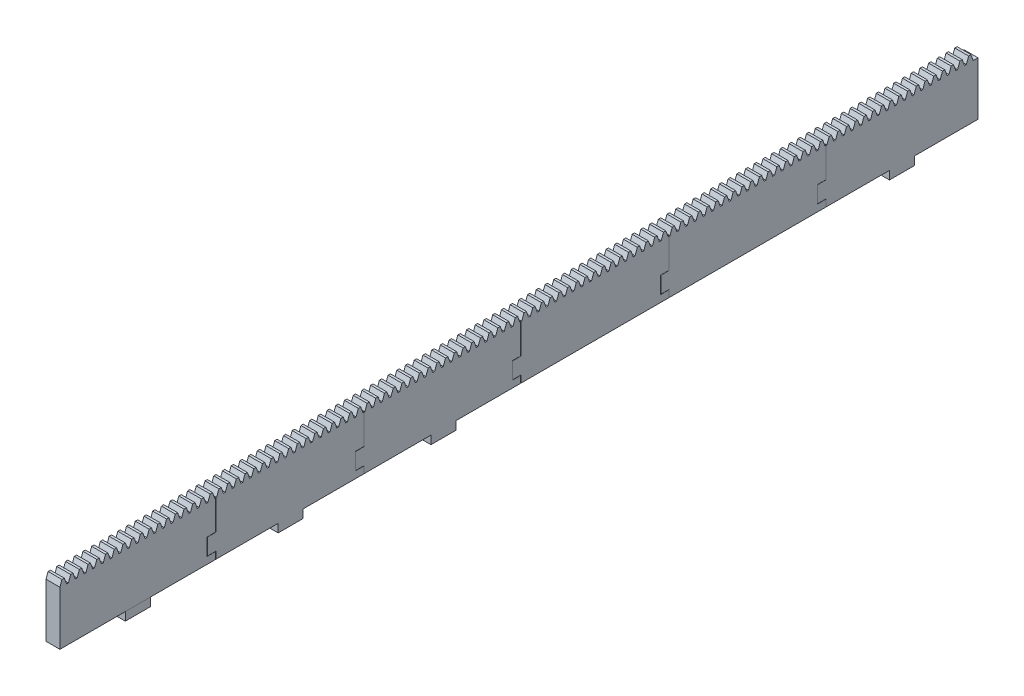
SolidWorks part; units mm, degrees
ref_plane "Спереди" through (0, 0, 0) normal (0, 0, 1) x (1, 0, 0)
ref_plane "Сверху" through (0, 0, 0) normal (0, 1, 0) x (1, 0, 0)
ref_plane "Справа" through (0, 0, 0) normal (1, 0, 0) x (0, 0, -1)
sketch "Эскиз2" plane through (0, 0, 0) normal (1, 0, 0) x (0, 0, -1)
  line L0 (-26.55, -90810.0672) -> (-26.55, -90381.6872) construction
  line L1 (-26.55, -90933.2872) -> (635.45, -90933.2872)
  line L2 (-26.55, -90933.2872) -> (-26.55, -90894.9119)
  line L3 (-26.55, -90894.9119) -> (635.45, -90894.9119)
  line L4 (635.45, -90933.2872) -> (635.45, -90894.9119)
  line L5 (635.45, -90810.0672) -> (635.45, -90381.6872) construction
  line L7 (-26.55, -90933.2872) -> (635.45, -90933.2872) construction
  dimension "D1" = 38.3753
  dimension "База_начала" = 26.55
  dimension "Длина_базы" = 662
  dimension "База_конца" = 635.45
  dimension "База_низа" = 90933.2872
extrude "Бобышка-Вытянуть1" add sketch "Эскиз2" along normal blind 10
sketch "Эскиз3" plane through (10, 0, 0) normal (1, 0, 0) x (0, 0, -1)
  line L0 (-26.55, -90894.9119) -> (-24.9125, -90890.4119)
  line L2 (-24.9125, -90890.4119) -> (-23.2265, -90890.4119)
  line L3 (-23.2265, -90890.4119) -> (-21.589, -90894.9119)
  line L4 (635.45, -90894.9119) -> (-26.55, -90894.9119) construction
  line L5 (-21.589, -90894.9119) -> (-26.55, -90894.9119)
  line L6 (-24.0695, -90890.4119) -> (-24.0695, -90894.9119) construction
  line L7 (-26.55, -90894.9119) -> (-26.55, -90933.2872) construction
  dimension "D1" = 1.686
  dimension "D2" = 4.961
  dimension "D3" = 4.5
extrude "Бобышка-Вытянуть2" add sketch "Эскиз3" against normal blind 10
pattern_linear "Линейный массив1" count 105 spacing 6.2832 along (0, 0, -1) of "Бобышка-Вытянуть2"
sketch "Лапки_рейки_эскиз" plane through (0, 0, 0) normal (1, 0, 0) x (0, 0, -1)
  line L0 (590.5046, -90933.2872) -> (570.5046, -90933.2872)
  line L1 (570.5046, -90933.2872) -> (570.5046, -90925.2872)
  line L2 (570.5046, -90925.2872) -> (590.5046, -90925.2872)
  line L3 (590.5046, -90925.2872) -> (590.5046, -90933.2872)
  line L4 (479.1606, -90933.2872) -> (459.1606, -90933.2872)
  line L5 (459.1606, -90933.2872) -> (459.1606, -90925.2872)
  line L6 (459.1606, -90925.2872) -> (479.1606, -90925.2872)
  line L7 (479.1606, -90925.2872) -> (479.1606, -90933.2872)
  line L8 (369.2048, -90933.2872) -> (349.2048, -90933.2872)
  line L9 (349.2048, -90933.2872) -> (349.2048, -90925.2872)
  line L10 (349.2048, -90925.2872) -> (369.2048, -90925.2872)
  line L11 (369.2048, -90925.2872) -> (369.2048, -90933.2872)
  line L12 (259.2491, -90933.2872) -> (239.2491, -90933.2872)
  line L13 (239.2491, -90933.2872) -> (239.2491, -90925.2872)
  line L14 (239.2491, -90925.2872) -> (259.2491, -90925.2872)
  line L15 (259.2491, -90925.2872) -> (259.2491, -90933.2872)
  line L16 (149.2933, -90933.2872) -> (129.2933, -90933.2872)
  line L17 (129.2933, -90933.2872) -> (129.2933, -90925.2872)
  line L18 (129.2933, -90925.2872) -> (149.2933, -90925.2872)
  line L19 (149.2933, -90925.2872) -> (149.2933, -90933.2872)
  line L20 (39.7431, -90933.2872) -> (19.7431, -90933.2872)
  line L21 (19.7431, -90933.2872) -> (19.7431, -90925.2872)
  line L22 (19.7431, -90925.2872) -> (39.7431, -90925.2872)
  line L23 (39.7431, -90925.2872) -> (39.7431, -90933.2872)
  dimension "X001" = 19.7431
  dimension "X002" = 20
  dimension "X003" = 89.5502
  dimension "X004" = 20
  dimension "X005" = 89.9557
  dimension "X006" = 20
  dimension "X007" = 89.9557
  dimension "X008" = 20
  dimension "X009" = 89.9557
  dimension "X010" = 20
  dimension "X011" = 91.3441
  dimension "X012" = 20
  dimension "Y001" = 90933.2872
  dimension "Y002" = 8
extrude "Лапки_рейки_к_полу" add sketch "Лапки_рейки_эскиз" against normal blind 22
sketch "Шипы_рейки_эскиз" plane through (0, 0, 0) normal (1, 0, 0) x (0, 0, -1)
  line L0 (548.0184, -90937.2872) -> (530.0184, -90937.2872)
  line L1 (530.0184, -90937.2872) -> (530.0184, -90933.2772)
  line L2 (530.0184, -90933.2772) -> (548.0184, -90933.2772)
  line L3 (548.0184, -90933.2772) -> (548.0184, -90937.2872)
  line L4 (436.6743, -90937.2872) -> (418.6743, -90937.2872)
  line L5 (418.6743, -90937.2872) -> (418.6743, -90933.2772)
  line L6 (418.6743, -90933.2772) -> (436.6743, -90933.2772)
  line L7 (436.6743, -90933.2772) -> (436.6743, -90937.2872)
  line L8 (326.7186, -90937.2872) -> (308.7186, -90937.2872)
  line L9 (308.7186, -90937.2872) -> (308.7186, -90933.2772)
  line L10 (308.7186, -90933.2772) -> (326.7186, -90933.2772)
  line L11 (326.7186, -90933.2772) -> (326.7186, -90937.2872)
  line L12 (216.7628, -90937.2872) -> (198.7628, -90937.2872)
  line L13 (198.7628, -90937.2872) -> (198.7628, -90933.2772)
  line L14 (198.7628, -90933.2772) -> (216.7628, -90933.2772)
  line L15 (216.7628, -90933.2772) -> (216.7628, -90937.2872)
  line L16 (106.8071, -90937.2872) -> (88.8071, -90937.2872)
  line L17 (88.8071, -90937.2872) -> (88.8071, -90933.2772)
  line L18 (88.8071, -90933.2772) -> (106.8071, -90933.2772)
  line L19 (106.8071, -90933.2772) -> (106.8071, -90937.2872)
  line L20 (-2.7431, -90937.2872) -> (-20.7431, -90937.2872)
  line L21 (-20.7431, -90937.2872) -> (-20.7431, -90933.2772)
  line L22 (-20.7431, -90933.2772) -> (-2.7431, -90933.2772)
  line L23 (-2.7431, -90933.2772) -> (-2.7431, -90937.2872)
  dimension "X001" = 20.7431
  dimension "X002" = 18
  dimension "X003" = 91.5502
  dimension "X004" = 18
  dimension "X005" = 91.9557
  dimension "X006" = 18
  dimension "X007" = 91.9557
  dimension "X008" = 18
  dimension "X009" = 91.9557
  dimension "X010" = 18
  dimension "X011" = 93.3441
  dimension "X012" = 18
  dimension "Y001" = 90937.2872
  dimension "Y002" = 4.01
extrude "Шипы_рейки_4мм" [suppressed] add sketch "Шипы_рейки_эскиз" along normal blind 10
sketch "Болты_рейки_эскиз" plane through (0, 0, 0) normal (0, 1, 0) x (1, 0, 0)
  line L0 (-22, 39.7431) -> (0, 19.7431) construction
  line L1 (-22, 19.7431) -> (0, 19.7431) construction
  line L2 (0, 0.2202) -> (-22, 19.7431) construction
  line L3 (0, 39.7431) -> (0, 19.7431) construction
  circle A0 centre (-11, 580.5046) radius 2.75
  circle A1 centre (-11, 469.1606) radius 2.75
  circle A2 centre (-11, 359.2048) radius 2.75
  circle A3 centre (-11, 249.2491) radius 2.75
  circle A4 centre (-11, 139.2933) radius 2.75
  circle A5 centre (-11, 29.7431) radius 2.75
  point P26 (-11, 29.7431)
  dimension "Диаметр001" = 5.5
  dimension "Диаметр002" = 5.5
  dimension "Диаметр003" = 5.5
  dimension "Диаметр004" = 5.5
  dimension "Диаметр005" = 5.5
  dimension "Диаметр006" = 5.5
  dimension "Y002" = 109.5502
  dimension "Y003" = 109.9557
  dimension "Y004" = 109.9557
  dimension "Y005" = 109.9557
  dimension "Y006" = 111.3441
extrude "Болты_рейки_М5" cut sketch "Болты_рейки_эскиз" against normal through all and the other way through all
sketch "Гайки_рейки_эскиз" plane through (0, -90925.2872, 0) normal (0, 1, 0) x (1, 0, 0)
  line L0 (-6.208, 580.5046) -> (-8.604, 576.3546)
  line L1 (-8.604, 576.3546) -> (-13.396, 576.3546)
  line L2 (-13.396, 576.3546) -> (-15.792, 580.5046)
  line L3 (-15.792, 580.5046) -> (-13.396, 584.6546)
  line L4 (-13.396, 584.6546) -> (-8.604, 584.6546)
  line L5 (-8.604, 584.6546) -> (-6.208, 580.5046)
  line L6 (-6.208, 469.1606) -> (-8.604, 465.0106)
  line L7 (-8.604, 465.0106) -> (-13.396, 465.0106)
  line L8 (-13.396, 465.0106) -> (-15.792, 469.1606)
  line L9 (-15.792, 469.1606) -> (-13.396, 473.3106)
  line L10 (-13.396, 473.3106) -> (-8.604, 473.3106)
  line L11 (-8.604, 473.3106) -> (-6.208, 469.1606)
  line L12 (-6.208, 359.2048) -> (-8.604, 355.0548)
  line L13 (-8.604, 355.0548) -> (-13.396, 355.0548)
  line L14 (-13.396, 355.0548) -> (-15.792, 359.2048)
  line L15 (-15.792, 359.2048) -> (-13.396, 363.3548)
  line L16 (-13.396, 363.3548) -> (-8.604, 363.3548)
  line L17 (-8.604, 363.3548) -> (-6.208, 359.2048)
  line L18 (-6.208, 249.2491) -> (-8.604, 245.0991)
  line L19 (-8.604, 245.0991) -> (-13.396, 245.0991)
  line L20 (-13.396, 245.0991) -> (-15.792, 249.2491)
  line L21 (-15.792, 249.2491) -> (-13.396, 253.3991)
  line L22 (-13.396, 253.3991) -> (-8.604, 253.3991)
  line L23 (-8.604, 253.3991) -> (-6.208, 249.2491)
  line L24 (-6.208, 139.2933) -> (-8.604, 135.1433)
  line L25 (-8.604, 135.1433) -> (-13.396, 135.1433)
  line L26 (-13.396, 135.1433) -> (-15.792, 139.2933)
  line L27 (-15.792, 139.2933) -> (-13.396, 143.4433)
  line L28 (-13.396, 143.4433) -> (-8.604, 143.4433)
  line L29 (-8.604, 143.4433) -> (-6.208, 139.2933)
  line L30 (-6.208, 29.7431) -> (-8.604, 25.5931)
  line L31 (-8.604, 25.5931) -> (-13.396, 25.5931)
  line L32 (-13.396, 25.5931) -> (-15.792, 29.7431)
  line L33 (-15.792, 29.7431) -> (-13.396, 33.8931)
  line L34 (-13.396, 33.8931) -> (-8.604, 33.8931)
  line L35 (-8.604, 33.8931) -> (-6.208, 29.7431)
  line L36 (-22, 39.7431) -> (-22, 19.7431) construction
  point P41 (-22, 29.7431)
  dimension "X001" = 15.792
  dimension "X002" = 2.396
  dimension "X003" = 4.792
  dimension "X004" = 2.396
  dimension "Y002" = 4.15
  dimension "Y003" = 4.15
  dimension "Y004" = 101.2502
  dimension "Y005" = 4.15
  dimension "Y006" = 4.15
  dimension "Y007" = 101.6557
  dimension "Y008" = 4.15
  dimension "Y009" = 4.15
  dimension "Y010" = 101.6557
  dimension "Y011" = 4.15
  dimension "Y012" = 4.15
  dimension "Y013" = 101.6557
  dimension "Y014" = 4.15
  dimension "Y015" = 4.15
  dimension "Y016" = 103.0441
  dimension "Y017" = 4.15
  dimension "Y018" = 4.15
extrude "Гайки_рейки_М5_4_3мм" cut sketch "Гайки_рейки_эскиз" against normal blind 4.3
sketch "Секции_рейки_эскиз" plane through (0, 0, 0) normal (1, 0, 0) x (0, 0, -1)
  line L0 (525.7842, -90938.2872) -> (525.6342, -90938.2872)
  line L1 (525.6342, -90938.2872) -> (525.6342, -90928.3622)
  line L2 (525.6342, -90928.3622) -> (519.6342, -90928.3622)
  line L3 (519.6342, -90928.3622) -> (519.6342, -90916.2122)
  line L4 (519.6342, -90916.2122) -> (525.6342, -90916.2122)
  line L5 (525.6342, -90916.2122) -> (525.6342, -90888.2872)
  line L6 (525.6342, -90888.2872) -> (525.7842, -90888.2872)
  line L7 (525.7842, -90888.2872) -> (525.7842, -90916.3622)
  line L8 (525.7842, -90916.3622) -> (519.7842, -90916.3622)
  line L9 (519.7842, -90916.3622) -> (519.7842, -90928.2122)
  line L10 (519.7842, -90928.2122) -> (525.7842, -90928.2122)
  line L11 (525.7842, -90928.2122) -> (525.7842, -90938.2872)
  line L12 (412.6869, -90938.2872) -> (412.5369, -90938.2872)
  line L13 (412.5369, -90938.2872) -> (412.5369, -90928.3622)
  line L14 (412.5369, -90928.3622) -> (406.5369, -90928.3622)
  line L15 (406.5369, -90928.3622) -> (406.5369, -90916.2122)
  line L16 (406.5369, -90916.2122) -> (412.5369, -90916.2122)
  line L17 (412.5369, -90916.2122) -> (412.5369, -90888.2872)
  line L18 (412.5369, -90888.2872) -> (412.6869, -90888.2872)
  line L19 (412.6869, -90888.2872) -> (412.6869, -90916.3622)
  line L20 (412.6869, -90916.3622) -> (406.6869, -90916.3622)
  line L21 (406.6869, -90916.3622) -> (406.6869, -90928.2122)
  line L22 (406.6869, -90928.2122) -> (412.6869, -90928.2122)
  line L23 (412.6869, -90928.2122) -> (412.6869, -90938.2872)
  line L24 (305.8727, -90938.2872) -> (305.7227, -90938.2872)
  line L25 (305.7227, -90938.2872) -> (305.7227, -90928.3622)
  line L26 (305.7227, -90928.3622) -> (299.7227, -90928.3622)
  line L27 (299.7227, -90928.3622) -> (299.7227, -90916.2122)
  line L28 (299.7227, -90916.2122) -> (305.7227, -90916.2122)
  line L29 (305.7227, -90916.2122) -> (305.7227, -90888.2872)
  line L30 (305.7227, -90888.2872) -> (305.8727, -90888.2872)
  line L31 (305.8727, -90888.2872) -> (305.8727, -90916.3622)
  line L32 (305.8727, -90916.3622) -> (299.8727, -90916.3622)
  line L33 (299.8727, -90916.3622) -> (299.8727, -90928.2122)
  line L34 (299.8727, -90928.2122) -> (305.8727, -90928.2122)
  line L35 (305.8727, -90928.2122) -> (305.8727, -90938.2872)
  line L36 (192.7754, -90938.2872) -> (192.6254, -90938.2872)
  line L37 (192.6254, -90938.2872) -> (192.6254, -90928.3622)
  line L38 (192.6254, -90928.3622) -> (186.6254, -90928.3622)
  line L39 (186.6254, -90928.3622) -> (186.6254, -90916.2122)
  line L40 (186.6254, -90916.2122) -> (192.6254, -90916.2122)
  line L41 (192.6254, -90916.2122) -> (192.6254, -90888.2872)
  line L42 (192.6254, -90888.2872) -> (192.7754, -90888.2872)
  line L43 (192.7754, -90888.2872) -> (192.7754, -90916.3622)
  line L44 (192.7754, -90916.3622) -> (186.7754, -90916.3622)
  line L45 (186.7754, -90916.3622) -> (186.7754, -90928.2122)
  line L46 (186.7754, -90928.2122) -> (192.7754, -90928.2122)
  line L47 (192.7754, -90928.2122) -> (192.7754, -90938.2872)
  line L48 (85.9612, -90938.2872) -> (85.8112, -90938.2872)
  line L49 (85.8112, -90938.2872) -> (85.8112, -90928.3622)
  line L50 (85.8112, -90928.3622) -> (79.8112, -90928.3622)
  line L51 (79.8112, -90928.3622) -> (79.8112, -90916.2122)
  line L52 (79.8112, -90916.2122) -> (85.8112, -90916.2122)
  line L53 (85.8112, -90916.2122) -> (85.8112, -90888.2872)
  line L54 (85.8112, -90888.2872) -> (85.9612, -90888.2872)
  line L55 (85.9612, -90888.2872) -> (85.9612, -90916.3622)
  line L56 (85.9612, -90916.3622) -> (79.9612, -90916.3622)
  line L57 (79.9612, -90916.3622) -> (79.9612, -90928.2122)
  line L58 (79.9612, -90928.2122) -> (85.9612, -90928.2122)
  line L59 (85.9612, -90928.2122) -> (85.9612, -90938.2872)
  dimension "X001" = 79.8112
  dimension "X002" = 0.15
  dimension "X003" = 5.85
  dimension "X004" = 0.15
  dimension "X005" = 100.6642
  dimension "X006" = 0.15
  dimension "X007" = 5.85
  dimension "X008" = 0.15
  dimension "X009" = 106.9473
  dimension "X010" = 0.15
  dimension "X011" = 5.85
  dimension "X012" = 0.15
  dimension "X013" = 100.6642
  dimension "X014" = 0.15
  dimension "X015" = 5.85
  dimension "X016" = 0.15
  dimension "X017" = 106.9473
  dimension "X018" = 0.15
  dimension "X019" = 5.85
  dimension "X020" = 0.15
  dimension "Y001" = 90938.2872
  dimension "Y002" = 9.925
  dimension "Y003" = 0.15
  dimension "Y004" = 11.85
  dimension "Y005" = 0.15
  dimension "Y006" = 27.925
extrude "Секции_рейки_шип_паз_6шт" cut sketch "Секции_рейки_эскиз" against normal through all and the other way through all
sketch "Торцы_рейки_эскиз" plane through (0, 0, 0) normal (1, 0, 0) x (0, 0, -1)
  line L0 (647.2604, -90939.2872) -> (635.3, -90939.2872)
  line L1 (635.3, -90939.2872) -> (635.3, -90883.2872)
  line L2 (635.3, -90883.2872) -> (647.2604, -90883.2872)
  line L3 (647.2604, -90883.2872) -> (647.2604, -90939.2872)
  line L4 (-26.4, -90939.2872) -> (-36.55, -90939.2872)
  line L5 (-36.55, -90939.2872) -> (-36.55, -90883.2872)
  line L6 (-36.55, -90883.2872) -> (-26.4, -90883.2872)
  line L7 (-26.4, -90883.2872) -> (-26.4, -90939.2872)
  dimension "X001" = 36.55
  dimension "X002" = 10.15
  dimension "X003" = 661.7
  dimension "X004" = 11.9604
  dimension "Y001" = 90939.2872
  dimension "Y002" = 56
extrude "Торцы_рейки_зазор_0_15мм" cut sketch "Торцы_рейки_эскиз" against normal through all and the other way through all
sketch "Эскиз5" plane through (0, -90933.2872, 0) normal (0, -1, 0) x (1, 0, 0)
  line L0 (10, 26.4) -> (10, -85.8112) construction
  line L1 (0, -20.7431) -> (10, -20.7431)
  line L2 (0, -20.7431) -> (0, -38.7431)
  line L3 (0, -38.7431) -> (10, -38.7431)
  line L4 (10, -20.7431) -> (10, -38.7431)
  line L5 (0, -19.7431) -> (0, -39.7431) construction
  line L6 (-22, -39.7431) -> (0, -39.7431) construction
  line L7 (0, -39.7431) -> (0, -85.8112) construction
  point P15 (0, -29.7431)
  point P16 (0, -29.7431)
  dimension "D1" = 18
extrude "Бобышка-Вытянуть6" add sketch "Эскиз5" along normal blind 6
pattern_linear "Линейный массив2" count 6 spacing 110.1523 along (0, 0, -1) of "Бобышка-Вытянуть6"
sketch "Эскиз6" plane through (0, -90933.2872, 0) normal (0, -1, 0) x (1, 0, 0)
  line L0 (0, -570.5046) -> (0, -590.5046) construction
  line L1 (10, -525.7842) -> (10, -635.3) construction
  line L2 (10, -571.5046) -> (0, -571.5046)
  line L3 (10, -571.5046) -> (10, -589.5046)
  line L4 (10, -589.5046) -> (0, -589.5046)
  line L5 (0, -571.5046) -> (0, -589.5046)
  point P4 (0, -580.5046)
  point P11 (0, -580.5046)
  point P12 (0, 0)
  dimension "D1" = 18
extrude "Бобышка-Вытянуть7" add sketch "Эскиз6" along normal blind 6
equation "\"Ширина груза\"= 160"
equation "\"Глубина груза\"= 240"
equation "\"Высота груза\"= 160"
equation "\"Ширина ячейки\"= \"Ширина груза\" + 10"
equation "\"Глубина ячейки\"= \"Глубина груза\" + 10"
equation "\"Высота ячейки\"= \"Высота груза\" + 10 + 13"
equation "\"Колво ячеек ширина\"= 2"
equation "\"Колво ячеек высота\"= 2"
equation "\"Толщина стенки\" = \"Толщина тонких панелей\""
equation "\"Крепление дверцы\"= 5 "
equation "\"Ширина рейки\"= \"Толщина шестерни\""
equation "\"Высота рейки\"= 20"
equation "\"Высота пола\" = 2*\"Толщина тонких панелей\""
equation "\"Колво полозьев\"= 5"
equation "\"Отступ рейки\"= 20"
equation "\"Глубина каретки\"= \"Глубина ячейки\" + 30 + \"Мотор Y высота корпуса\" + 20"
equation "\"Длинна рейки\" = (\"Ширина ячейки\"+\"Толщина вертикальных стенок\"+\"Крепление дверцы\")*\"Колво ячеек ширина\"+\"Ширина ячейки выгрузки\"*\"Колво выгрузки\"+\"Толщина вертикальных стенок\"+2*\"Отступ крепления мотора фиксации\"-\"Крепление дверцы\"*\"Колво ячеек ширина\""
equation "\"Отступ шпильки\"= 26"
equation "\"Диаметр шпильки\"= 5"
equation "\"Длинна шпильки\" = (\"Высота ячейки\"+\"Толщина горизонтальных плит\"+\"Высота пола\")*\"Колво ячеек высота\"+2*(\"Толщина горизонтальных плит\"+\"Отступ рейки\")"
equation "\"Ширина пластины\"= 50  "
equation "\"Высота зона выгрузки\"= \"Высота ячейки\" * 2 + \"Толщина стенки\" * 2"
equation "\"Колво выгрузки\"= 1"
equation "\"Ширина ячейки выгрузки\" = \"Ширина ячейки\"+\"Толщина вертикальных стенок\"+2*\"Отступ крепления мотора фиксации\""
equation "\"Отступ крепления мотора фиксации\" = (\"Ширина пластины\"+20-\"Толщина вертикальных стенок\")/2"
equation "\"Мотор X ширина корпуса\"= 42.3"
equation "\"Мотор X высота корпуса\"= 42.3"
equation "\"Мотор X длина корпуса\"= 40"
equation "\"Мотор X вылет вала\"= 19.8"
equation "\"Мотор Y ширина корпуса\"= 42.3"
equation "\"Мотор Y высота корпуса\"= 42.3"
equation "\"Мотор Y длина корпуса\"= 48"
equation "\"Мотор Y вылет вала\"= 30"
equation "\"Мотор Z ширина корпуса\"= 42"
equation "\"Мотор Z высота корпуса\"= 42"
equation "\"Мотор Z длина корпуса\"= 40"
equation "\"Мотор Z вылет вала\"= 23"
equation "\"Мотор диаметр вала ПРЕДВ\"= 5"
equation "\"Мотор шаг крепления ПРЕДВ\"= 31"
equation "\"Мотор диаметр отверстий ПРЕДВ\"= 3"
equation "\"Мотор глубина отверстий ПРЕДВ\"= 4.5"
equation "\"Мотор диаметр буртика ПРЕДВ\"= 22"
equation "\"Мотор высота буртика ПРЕДВ\"= 2"
equation "\"Мотор диаметр шкива ПРЕДВ\"= 16"
equation "\"Мотор длина шкива ПРЕДВ\"= 12"
equation "\"Мотор отступ шкива ПРЕДВ\"= 5"
equation "\"Мотор X шаг градусов\"= 1.8"
equation "\"Мотор Y шаг градусов\"= 1.8"
equation "\"Мотор Z шаг градусов\"= 1.8"
equation "\"Мотор Y диаметр ротора\"= 25.78"
equation "\"Толщина шестерни\"= 10"
equation "\"D1@Эскиз2\" = \"Высота рейки от пола\""
equation "\"D1@Бобышка-Вытянуть1\"=\"Толщина шестерни\""
equation "\"D1@Бобышка-Вытянуть2\"=\"Толщина шестерни\""
equation "\"Высота рейки от пола\"= 38.3752522580543"
equation "\"X001@Лапки_рейки_эскиз\" = \"Привязка_X001_Лапки_рейки_эскиз\""
equation "\"X003@Лапки_рейки_эскиз\" = -1*((\"Крепление рейки 2\"-\"Смещение рейки по Z\"+(10))-(\"Крепление рейки 1\"-\"Смещение рейки по Z\"+(-10)))"
equation "\"X005@Лапки_рейки_эскиз\" = -1*((\"Крепление рейки 3\"-\"Смещение рейки по Z\"+(10))-(\"Крепление рейки 2\"-\"Смещение рейки по Z\"+(-10)))"
equation "\"X007@Лапки_рейки_эскиз\" = -1*((\"Крепление рейки 4\"-\"Смещение рейки по Z\"+(10))-(\"Крепление рейки 3\"-\"Смещение рейки по Z\"+(-10)))"
equation "\"X009@Лапки_рейки_эскиз\" = -1*((\"Крепление рейки 5\"-\"Смещение рейки по Z\"+(10))-(\"Крепление рейки 4\"-\"Смещение рейки по Z\"+(-10)))"
equation "\"X011@Лапки_рейки_эскиз\" = -1*((\"Крепление рейки 6\"-\"Смещение рейки по Z\"+(10))-(\"Крепление рейки 5\"-\"Смещение рейки по Z\"+(-10)))"
equation "\"X001@Шипы_рейки_эскиз\" = \"Привязка_X001_Шипы_рейки_эскиз\""
equation "\"X003@Шипы_рейки_эскиз\" = -1*((\"Крепление рейки 2\"-\"Смещение рейки по Z\"+(9))-(\"Крепление рейки 1\"-\"Смещение рейки по Z\"+(-9)))"
equation "\"X005@Шипы_рейки_эскиз\" = -1*((\"Крепление рейки 3\"-\"Смещение рейки по Z\"+(9))-(\"Крепление рейки 2\"-\"Смещение рейки по Z\"+(-9)))"
equation "\"X007@Шипы_рейки_эскиз\" = -1*((\"Крепление рейки 4\"-\"Смещение рейки по Z\"+(9))-(\"Крепление рейки 3\"-\"Смещение рейки по Z\"+(-9)))"
equation "\"X009@Шипы_рейки_эскиз\" = -1*((\"Крепление рейки 5\"-\"Смещение рейки по Z\"+(9))-(\"Крепление рейки 4\"-\"Смещение рейки по Z\"+(-9)))"
equation "\"X011@Шипы_рейки_эскиз\" = -1*((\"Крепление рейки 6\"-\"Смещение рейки по Z\"+(9))-(\"Крепление рейки 5\"-\"Смещение рейки по Z\"+(-9)))"
equation "\"Y002@Болты_рейки_эскиз\" = -1*((\"Крепление рейки 2\"-\"Смещение рейки по Z\"+(0))-(\"Крепление рейки 1\"-\"Смещение рейки по Z\"+(0)))"
equation "\"Y003@Болты_рейки_эскиз\" = -1*((\"Крепление рейки 3\"-\"Смещение рейки по Z\"+(0))-(\"Крепление рейки 2\"-\"Смещение рейки по Z\"+(0)))"
equation "\"Y004@Болты_рейки_эскиз\" = -1*((\"Крепление рейки 4\"-\"Смещение рейки по Z\"+(0))-(\"Крепление рейки 3\"-\"Смещение рейки по Z\"+(0)))"
equation "\"Y005@Болты_рейки_эскиз\" = -1*((\"Крепление рейки 5\"-\"Смещение рейки по Z\"+(0))-(\"Крепление рейки 4\"-\"Смещение рейки по Z\"+(0)))"
equation "\"Y006@Болты_рейки_эскиз\" = -1*((\"Крепление рейки 6\"-\"Смещение рейки по Z\"+(0))-(\"Крепление рейки 5\"-\"Смещение рейки по Z\"+(0)))"
equation "\"Y004@Гайки_рейки_эскиз\" = -1*((\"Крепление рейки 2\"-\"Смещение рейки по Z\"+(4.15))-(\"Крепление рейки 1\"-\"Смещение рейки по Z\"+(-4.15)))"
equation "\"Y007@Гайки_рейки_эскиз\" = -1*((\"Крепление рейки 3\"-\"Смещение рейки по Z\"+(4.15))-(\"Крепление рейки 2\"-\"Смещение рейки по Z\"+(-4.15)))"
equation "\"Y010@Гайки_рейки_эскиз\" = -1*((\"Крепление рейки 4\"-\"Смещение рейки по Z\"+(4.15))-(\"Крепление рейки 3\"-\"Смещение рейки по Z\"+(-4.15)))"
equation "\"Y013@Гайки_рейки_эскиз\" = -1*((\"Крепление рейки 5\"-\"Смещение рейки по Z\"+(4.15))-(\"Крепление рейки 4\"-\"Смещение рейки по Z\"+(-4.15)))"
equation "\"Y016@Гайки_рейки_эскиз\" = -1*((\"Крепление рейки 6\"-\"Смещение рейки по Z\"+(4.15))-(\"Крепление рейки 5\"-\"Смещение рейки по Z\"+(-4.15)))"
equation "\"X003@Торцы_рейки_эскиз\" = \"Длина рейки для печати\""
equation "\"Толщина тонких панелей\" = 6"
equation "\"Толщина вертикальных стенок\" = 6"
equation "\"Толщина горизонтальных плит\" = 6"
equation "\"Базовая высота корпуса\"= (\"Высота ячейки\"+\"Толщина тонких панелей\"+\"Высота пола\")*\"Колво ячеек высота\"+6*\"Толщина тонких панелей\"+\"Мотор X ширина корпуса\"+\"Мотор Y ширина корпуса\"+75"
equation "\"Высота корпуса\"= (\"Высота ячейки\"+\"Толщина горизонтальных плит\"+\"Высота пола\")*\"Колво ячеек высота\"+2*\"Толщина горизонтальных плит\"+4*\"Толщина тонких панелей\"+\"Мотор X ширина корпуса\"+\"Мотор Y ширина корпуса\"+75"
equation "\"Смещение центра корпуса\"= (\"Высота корпуса\"-\"Базовая высота корпуса\")/2-(\"Толщина горизонтальных плит\"-\"Толщина тонких панелей\")"
equation "\"Отметка пола\"= -\"Базовая высота корпуса\"/2+\"Толщина тонких панелей\""
equation "\"Отметка потолка\"= \"Отметка пола\"+\"Высота корпуса\"-2*\"Толщина горизонтальных плит\""
equation "\"Отметка верхней полки\"= \"Отметка потолка\"-(28+\"Толщина тонких панелей\")-\"Высота ячейки\"-\"Высота пола\""
equation "\"Отметка нижней полки\"= \"Отметка верхней полки\"-\"Высота ячейки\"-\"Высота пола\"-\"Толщина горизонтальных плит\""
equation "\"X001@Торцы_рейки_эскиз\" = \"Длинна рейки\"-\"База_конца@Эскиз2\"+10"
equation "\"dT\"= (\"Толщина вертикальных стенок\"-\"Толщина тонких панелей\")"
equation "\"dW\"= \"Ширина ячейки\"-430+2*\"dT\"/3"
equation "\"Торцевой зазор рейки\"= 0.15"
equation "\"Зазор стыка рейки\"= 0.15"
equation "\"Длина шипа стыка рейки\"= 6"
equation "\"Шаг зубьев рейки\"= 2*pi"
equation "\"Начало рейки для печати\"= \"Длинна рейки\"-\"База_конца@Эскиз2\"-\"Торцевой зазор рейки\""
equation "\"Длина рейки для печати\"= \"Длинна рейки\"-2*\"Торцевой зазор рейки\""
equation "\"Ноль впадин рейки\"= \"Длинна рейки\"-\"База_конца@Эскиз2\"-(\"D2@Эскиз3\"+\"Шаг зубьев рейки\")/2"
equation "\"Стык рейки 1\"= \"Ноль впадин рейки\"-\"Шаг зубьев рейки\"*int((\"Ноль впадин рейки\"-(\"Начало рейки для печати\"-1*\"Длина рейки для печати\"/6))/\"Шаг зубьев рейки\"+0.5)"
equation "\"Стык рейки 2\"= \"Ноль впадин рейки\"-\"Шаг зубьев рейки\"*int((\"Ноль впадин рейки\"-(\"Начало рейки для печати\"-2*\"Длина рейки для печати\"/6))/\"Шаг зубьев рейки\"+0.5)"
equation "\"Стык рейки 3\"= \"Ноль впадин рейки\"-\"Шаг зубьев рейки\"*int((\"Ноль впадин рейки\"-(\"Начало рейки для печати\"-3*\"Длина рейки для печати\"/6))/\"Шаг зубьев рейки\"+0.5)"
equation "\"Стык рейки 4\"= \"Ноль впадин рейки\"-\"Шаг зубьев рейки\"*int((\"Ноль впадин рейки\"-(\"Начало рейки для печати\"-4*\"Длина рейки для печати\"/6))/\"Шаг зубьев рейки\"+0.5)"
equation "\"Стык рейки 5\"= \"Ноль впадин рейки\"-\"Шаг зубьев рейки\"*int((\"Ноль впадин рейки\"-(\"Начало рейки для печати\"-5*\"Длина рейки для печати\"/6))/\"Шаг зубьев рейки\"+0.5)"
equation "\"X001@Секции_рейки_эскиз\" = 1*((\"Стык рейки 1\"+\"Длина шипа стыка рейки\"+\"Зазор стыка рейки\"/2)-0)"
equation "\"X002@Секции_рейки_эскиз\" = -1*((\"Стык рейки 1\"+\"Длина шипа стыка рейки\"-\"Зазор стыка рейки\"/2)-(\"Стык рейки 1\"+\"Длина шипа стыка рейки\"+\"Зазор стыка рейки\"/2))"
equation "\"X003@Секции_рейки_эскиз\" = -1*((\"Стык рейки 1\"+\"Зазор стыка рейки\"/2)-(\"Стык рейки 1\"+\"Длина шипа стыка рейки\"-\"Зазор стыка рейки\"/2))"
equation "\"X004@Секции_рейки_эскиз\" = -1*((\"Стык рейки 1\"-\"Зазор стыка рейки\"/2)-(\"Стык рейки 1\"+\"Зазор стыка рейки\"/2))"
equation "\"X005@Секции_рейки_эскиз\" = -1*((\"Стык рейки 2\"+\"Длина шипа стыка рейки\"+\"Зазор стыка рейки\"/2)-(\"Стык рейки 1\"-\"Зазор стыка рейки\"/2))"
equation "\"X006@Секции_рейки_эскиз\" = -1*((\"Стык рейки 2\"+\"Длина шипа стыка рейки\"-\"Зазор стыка рейки\"/2)-(\"Стык рейки 2\"+\"Длина шипа стыка рейки\"+\"Зазор стыка рейки\"/2))"
equation "\"X007@Секции_рейки_эскиз\" = -1*((\"Стык рейки 2\"+\"Зазор стыка рейки\"/2)-(\"Стык рейки 2\"+\"Длина шипа стыка рейки\"-\"Зазор стыка рейки\"/2))"
equation "\"X008@Секции_рейки_эскиз\" = -1*((\"Стык рейки 2\"-\"Зазор стыка рейки\"/2)-(\"Стык рейки 2\"+\"Зазор стыка рейки\"/2))"
equation "\"X009@Секции_рейки_эскиз\" = -1*((\"Стык рейки 3\"+\"Длина шипа стыка рейки\"+\"Зазор стыка рейки\"/2)-(\"Стык рейки 2\"-\"Зазор стыка рейки\"/2))"
equation "\"X010@Секции_рейки_эскиз\" = -1*((\"Стык рейки 3\"+\"Длина шипа стыка рейки\"-\"Зазор стыка рейки\"/2)-(\"Стык рейки 3\"+\"Длина шипа стыка рейки\"+\"Зазор стыка рейки\"/2))"
equation "\"X011@Секции_рейки_эскиз\" = -1*((\"Стык рейки 3\"+\"Зазор стыка рейки\"/2)-(\"Стык рейки 3\"+\"Длина шипа стыка рейки\"-\"Зазор стыка рейки\"/2))"
equation "\"X012@Секции_рейки_эскиз\" = -1*((\"Стык рейки 3\"-\"Зазор стыка рейки\"/2)-(\"Стык рейки 3\"+\"Зазор стыка рейки\"/2))"
equation "\"X013@Секции_рейки_эскиз\" = -1*((\"Стык рейки 4\"+\"Длина шипа стыка рейки\"+\"Зазор стыка рейки\"/2)-(\"Стык рейки 3\"-\"Зазор стыка рейки\"/2))"
equation "\"X014@Секции_рейки_эскиз\" = -1*((\"Стык рейки 4\"+\"Длина шипа стыка рейки\"-\"Зазор стыка рейки\"/2)-(\"Стык рейки 4\"+\"Длина шипа стыка рейки\"+\"Зазор стыка рейки\"/2))"
equation "\"X015@Секции_рейки_эскиз\" = -1*((\"Стык рейки 4\"+\"Зазор стыка рейки\"/2)-(\"Стык рейки 4\"+\"Длина шипа стыка рейки\"-\"Зазор стыка рейки\"/2))"
equation "\"X016@Секции_рейки_эскиз\" = -1*((\"Стык рейки 4\"-\"Зазор стыка рейки\"/2)-(\"Стык рейки 4\"+\"Зазор стыка рейки\"/2))"
equation "\"X017@Секции_рейки_эскиз\" = -1*((\"Стык рейки 5\"+\"Длина шипа стыка рейки\"+\"Зазор стыка рейки\"/2)-(\"Стык рейки 4\"-\"Зазор стыка рейки\"/2))"
equation "\"X018@Секции_рейки_эскиз\" = -1*((\"Стык рейки 5\"+\"Длина шипа стыка рейки\"-\"Зазор стыка рейки\"/2)-(\"Стык рейки 5\"+\"Длина шипа стыка рейки\"+\"Зазор стыка рейки\"/2))"
equation "\"X019@Секции_рейки_эскиз\" = -1*((\"Стык рейки 5\"+\"Зазор стыка рейки\"/2)-(\"Стык рейки 5\"+\"Длина шипа стыка рейки\"-\"Зазор стыка рейки\"/2))"
equation "\"X020@Секции_рейки_эскиз\" = -1*((\"Стык рейки 5\"-\"Зазор стыка рейки\"/2)-(\"Стык рейки 5\"+\"Зазор стыка рейки\"/2))"
equation "\"Правый конец рейки\"= -\"Ширина ячейки\"-65"
equation "\"Левый конец рейки\"= \"Правый конец рейки\"+\"Длинна рейки\""
equation "\"Впадина рейки в сборке\"= \"Левый конец рейки\"-(\"Шаг зубьев рейки\"+4.961)/2"
equation "\"Стык рейки в сборке 1\"= \"Впадина рейки в сборке\"-\"Шаг зубьев рейки\"*int((\"Впадина рейки в сборке\"-(\"Левый конец рейки\"-0.15-1*(\"Длинна рейки\"-0.3)/6))/\"Шаг зубьев рейки\"+0.5)"
equation "\"Стык рейки в сборке 2\"= \"Впадина рейки в сборке\"-\"Шаг зубьев рейки\"*int((\"Впадина рейки в сборке\"-(\"Левый конец рейки\"-0.15-2*(\"Длинна рейки\"-0.3)/6))/\"Шаг зубьев рейки\"+0.5)"
equation "\"Стык рейки в сборке 3\"= \"Впадина рейки в сборке\"-\"Шаг зубьев рейки\"*int((\"Впадина рейки в сборке\"-(\"Левый конец рейки\"-0.15-3*(\"Длинна рейки\"-0.3)/6))/\"Шаг зубьев рейки\"+0.5)"
equation "\"Стык рейки в сборке 4\"= \"Впадина рейки в сборке\"-\"Шаг зубьев рейки\"*int((\"Впадина рейки в сборке\"-(\"Левый конец рейки\"-0.15-4*(\"Длинна рейки\"-0.3)/6))/\"Шаг зубьев рейки\"+0.5)"
equation "\"Стык рейки в сборке 5\"= \"Впадина рейки в сборке\"-\"Шаг зубьев рейки\"*int((\"Впадина рейки в сборке\"-(\"Левый конец рейки\"-0.15-5*(\"Длинна рейки\"-0.3)/6))/\"Шаг зубьев рейки\"+0.5)"
equation "\"Крепление рейки 1\"= (\"Левый конец рейки\"-0.15+\"Стык рейки в сборке 1\")/2"
equation "\"Крепление рейки 2\"= (\"Стык рейки в сборке 1\"+\"Стык рейки в сборке 2\")/2"
equation "\"Крепление рейки 3\"= (\"Стык рейки в сборке 2\"+\"Стык рейки в сборке 3\")/2"
equation "\"Крепление рейки 4\"= (\"Стык рейки в сборке 3\"+\"Стык рейки в сборке 4\")/2"
equation "\"Крепление рейки 5\"= (\"Стык рейки в сборке 4\"+\"Стык рейки в сборке 5\")/2"
equation "\"Крепление рейки 6\"= (\"Стык рейки в сборке 5\"+\"Правый конец рейки\"+0.15)/2"
equation "\"Смещение рейки по Z\"= \"База_конца@Эскиз2\"+\"Правый конец рейки\""
equation "\"Привязка_X001_Лапки_рейки_эскиз\"= 1*((\"Крепление рейки 1\"-\"Смещение рейки по Z\"+(10))-0)"
equation "\"X002@Лапки_рейки_эскиз\" = -1*((\"Крепление рейки 1\"-\"Смещение рейки по Z\"+(-10))-(\"Крепление рейки 1\"-\"Смещение рейки по Z\"+(10)))"
equation "\"X004@Лапки_рейки_эскиз\" = -1*((\"Крепление рейки 2\"-\"Смещение рейки по Z\"+(-10))-(\"Крепление рейки 2\"-\"Смещение рейки по Z\"+(10)))"
equation "\"X006@Лапки_рейки_эскиз\" = -1*((\"Крепление рейки 3\"-\"Смещение рейки по Z\"+(-10))-(\"Крепление рейки 3\"-\"Смещение рейки по Z\"+(10)))"
equation "\"X008@Лапки_рейки_эскиз\" = -1*((\"Крепление рейки 4\"-\"Смещение рейки по Z\"+(-10))-(\"Крепление рейки 4\"-\"Смещение рейки по Z\"+(10)))"
equation "\"X010@Лапки_рейки_эскиз\" = -1*((\"Крепление рейки 5\"-\"Смещение рейки по Z\"+(-10))-(\"Крепление рейки 5\"-\"Смещение рейки по Z\"+(10)))"
equation "\"X012@Лапки_рейки_эскиз\" = -1*((\"Крепление рейки 6\"-\"Смещение рейки по Z\"+(-10))-(\"Крепление рейки 6\"-\"Смещение рейки по Z\"+(10)))"
equation "\"Привязка_X001_Шипы_рейки_эскиз\"= 1*((\"Крепление рейки 1\"-\"Смещение рейки по Z\"+(9))-0)"
equation "\"X002@Шипы_рейки_эскиз\" = -1*((\"Крепление рейки 1\"-\"Смещение рейки по Z\"+(-9))-(\"Крепление рейки 1\"-\"Смещение рейки по Z\"+(9)))"
equation "\"X004@Шипы_рейки_эскиз\" = -1*((\"Крепление рейки 2\"-\"Смещение рейки по Z\"+(-9))-(\"Крепление рейки 2\"-\"Смещение рейки по Z\"+(9)))"
equation "\"X006@Шипы_рейки_эскиз\" = -1*((\"Крепление рейки 3\"-\"Смещение рейки по Z\"+(-9))-(\"Крепление рейки 3\"-\"Смещение рейки по Z\"+(9)))"
equation "\"X008@Шипы_рейки_эскиз\" = -1*((\"Крепление рейки 4\"-\"Смещение рейки по Z\"+(-9))-(\"Крепление рейки 4\"-\"Смещение рейки по Z\"+(9)))"
equation "\"X010@Шипы_рейки_эскиз\" = -1*((\"Крепление рейки 5\"-\"Смещение рейки по Z\"+(-9))-(\"Крепление рейки 5\"-\"Смещение рейки по Z\"+(9)))"
equation "\"X012@Шипы_рейки_эскиз\" = -1*((\"Крепление рейки 6\"-\"Смещение рейки по Z\"+(-9))-(\"Крепление рейки 6\"-\"Смещение рейки по Z\"+(9)))"
equation "\"Привязка_Y001_Болты_рейки_эскиз\"= 1*((\"Крепление рейки 1\"-\"Смещение рейки по Z\"+(0))-0)"
equation "\"Привязка_Y001_Гайки_рейки_эскиз\"= 1*((\"Крепление рейки 1\"-\"Смещение рейки по Z\"+(4.15))-0)"
equation "\"Y002@Гайки_рейки_эскиз\" = -1*((\"Крепление рейки 1\"-\"Смещение рейки по Z\"+(0))-(\"Крепление рейки 1\"-\"Смещение рейки по Z\"+(4.15)))"
equation "\"Y003@Гайки_рейки_эскиз\" = -1*((\"Крепление рейки 1\"-\"Смещение рейки по Z\"+(-4.15))-(\"Крепление рейки 1\"-\"Смещение рейки по Z\"+(0)))"
equation "\"Y005@Гайки_рейки_эскиз\" = -1*((\"Крепление рейки 2\"-\"Смещение рейки по Z\"+(0))-(\"Крепление рейки 2\"-\"Смещение рейки по Z\"+(4.15)))"
equation "\"Y006@Гайки_рейки_эскиз\" = -1*((\"Крепление рейки 2\"-\"Смещение рейки по Z\"+(-4.15))-(\"Крепление рейки 2\"-\"Смещение рейки по Z\"+(0)))"
equation "\"Y008@Гайки_рейки_эскиз\" = -1*((\"Крепление рейки 3\"-\"Смещение рейки по Z\"+(0))-(\"Крепление рейки 3\"-\"Смещение рейки по Z\"+(4.15)))"
equation "\"Y009@Гайки_рейки_эскиз\" = -1*((\"Крепление рейки 3\"-\"Смещение рейки по Z\"+(-4.15))-(\"Крепление рейки 3\"-\"Смещение рейки по Z\"+(0)))"
equation "\"Y011@Гайки_рейки_эскиз\" = -1*((\"Крепление рейки 4\"-\"Смещение рейки по Z\"+(0))-(\"Крепление рейки 4\"-\"Смещение рейки по Z\"+(4.15)))"
equation "\"Y012@Гайки_рейки_эскиз\" = -1*((\"Крепление рейки 4\"-\"Смещение рейки по Z\"+(-4.15))-(\"Крепление рейки 4\"-\"Смещение рейки по Z\"+(0)))"
equation "\"Y014@Гайки_рейки_эскиз\" = -1*((\"Крепление рейки 5\"-\"Смещение рейки по Z\"+(0))-(\"Крепление рейки 5\"-\"Смещение рейки по Z\"+(4.15)))"
equation "\"Y015@Гайки_рейки_эскиз\" = -1*((\"Крепление рейки 5\"-\"Смещение рейки по Z\"+(-4.15))-(\"Крепление рейки 5\"-\"Смещение рейки по Z\"+(0)))"
equation "\"Y017@Гайки_рейки_эскиз\" = -1*((\"Крепление рейки 6\"-\"Смещение рейки по Z\"+(0))-(\"Крепление рейки 6\"-\"Смещение рейки по Z\"+(4.15)))"
equation "\"Y018@Гайки_рейки_эскиз\" = -1*((\"Крепление рейки 6\"-\"Смещение рейки по Z\"+(-4.15))-(\"Крепление рейки 6\"-\"Смещение рейки по Z\"+(0)))"
equation "\"Y001@Лапки_рейки_эскиз\" = \"База_низа@Эскиз2\"-(0)"
equation "\"Y001@Шипы_рейки_эскиз\" = \"База_низа@Эскиз2\"-(-4)"
equation "\"Y001@Секции_рейки_эскиз\" = \"База_низа@Эскиз2\"-(-5)"
equation "\"Y001@Торцы_рейки_эскиз\" = \"База_низа@Эскиз2\"-(-6)"
